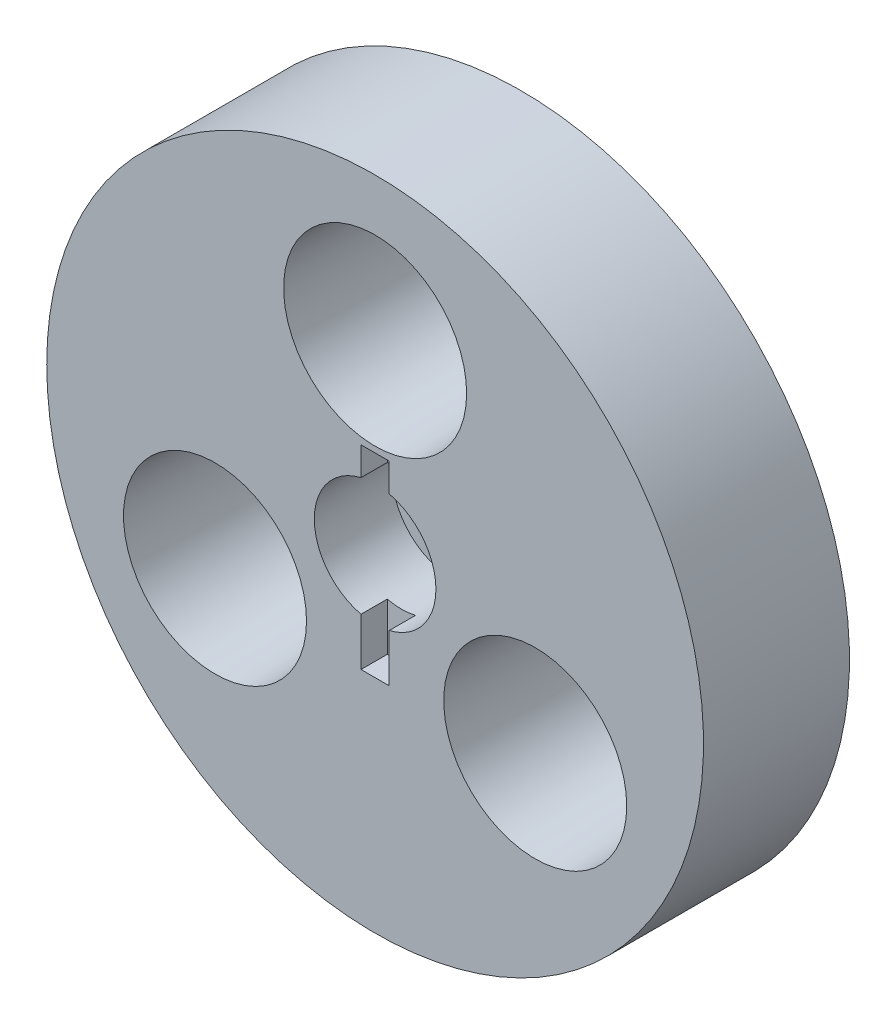
SolidWorks part; units mm, degrees
material "Teak"
ref_plane "Front Plane" through (0, 0, 0) normal (0, 0, 1) x (1, 0, 0)
ref_plane "Top Plane" through (0, 0, 0) normal (0, 1, 0) x (1, 0, 0)
ref_plane "Right Plane" through (0, 0, 0) normal (1, 0, 0) x (0, 0, -1)
sketch "Sketch1" plane through (0, 0, 0) normal (0, 0, 1) x (1, 0, 0)
  line L0 (0, 0) -> (20.8972, -12.065) construction
  line L1 (0, 42.8625) -> (0, -42.8625) construction
  line L2 (0, 0) -> (-20.8972, -12.065) construction
  line L3 (0, 24.13) -> (0, 0)
  circle A0 centre (0, 0) radius 42.8625
  circle A1 centre (0, 24.13) radius 11.1125
  circle A2 centre (-20.8972, -12.065) radius 11.1125
  circle A3 centre (20.8972, -12.065) radius 11.1125
  dimension "D3" = 85.725
  dimension "D5" = 22.225
  dimension "D1" = 120
  dimension "D2" = 120
  dimension "D4" = 24.13
extrude "Boss-Extrude1" add sketch "Sketch1" along normal mid plane 19.05 contours A0 A3 A2 A1 region at (-41.6502, 0, 0)
sketch "Sketch2" plane through (0, 0, 9.525) normal (0, 0, 1) x (1, 0, 0)
  circle A0 centre (0, 0) radius 7.9375
  dimension "D1" = 15.875
extrude "Cut-Extrude1" cut sketch "Sketch2" against normal blind 10.16
sketch "Sketch3" plane through (0, 0, 9.525) normal (0, 0, 1) x (1, 0, 0)
  line L0 (0, 11.43) -> (0, -13.97) construction
  line L1 (1.8415, 11.43) -> (-1.8415, 11.43)
  line L2 (1.8415, 11.43) -> (1.8415, -13.97)
  line L3 (1.8415, -13.97) -> (-1.8415, -13.97)
  line L4 (-1.8415, 11.43) -> (-1.8415, -13.97)
  circle A0 centre (0, 24.13) radius 11.1125 construction
  dimension "D1" = 3.683
  dimension "D2" = 25.4
  dimension "D3" = 12.7
extrude "Cut-Extrude2" cut sketch "Sketch3" against normal blind 3.429
draft "Draft2" type of draft neutral plane draft angle 2.5 faces to draft 3 face at (-9.7847, -12.065, 9.525) face at (32.0097, -12.065, 9.525) face at (11.1125, 24.13, 9.525) neutral plane through (0, 0, -9.525) neutral plane normal (0, 0, -1) reverse direction yes parameters "D1"=2.5
